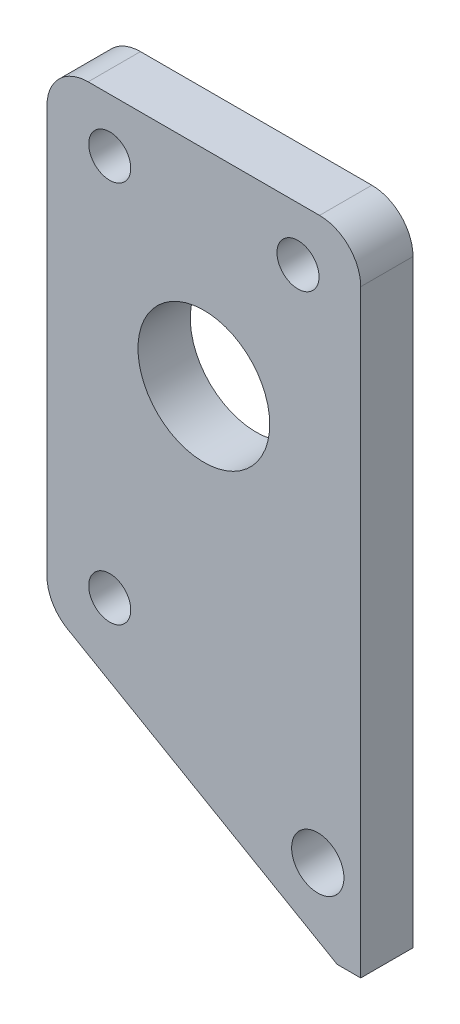
SolidWorks part; units mm, degrees
material "6061-T6 (SS)"
ref_plane "Front" through (0, 0, 0) normal (0, 0, 1) x (1, 0, 0)
ref_plane "Top" through (0, 0, 0) normal (0, 1, 0) x (1, 0, 0)
ref_plane "Right" through (0, 0, 0) normal (1, 0, 0) x (0, 0, -1)
ref_axis "side-side" through (80.9, 0, 0) along (-1, 0, 0)
ref_axis "up-down" through (0, 50, 0) along (0, -1, 0)
ref_axis "front-back" through (0, 0, -80.9) along (0, 0, 1)
sketch "Sketch4" plane through (0, 0, 0) normal (0, 0, 1) x (1, 0, 0)
  line L2 (23.3591, -238.4) -> (20.1841, -238.4)
  line L3 (20.1841, -238.4) -> (20.1841, -258.4435)
  line L5 (-176.6409, -178.2) -> (23.3591, -178.2)
  circle A2 centre (13.8341, -246.4) radius 3.175
  arc A3 (20.1841, -258.4435) -> (-67.8159, -304.4) centre (-11.8159, -304.4) ccw
sketch "Sketch1" plane through (0, 0, 0) normal (0, 0, 1) x (1, 0, 0)
  line L0 (16.1841, -255.9026) -> (-19.05, -235.5602)
  line L2 (-19.05, -178.2) -> (-19.05, -235.5602)
  line L3 (16.1841, -255.9026) -> (19.05, -255.9026)
  line L4 (19.05, -178.2) -> (19.05, -255.9026)
  line L5 (-176.6409, -178.2) -> (23.3591, -178.2) construction
  line L6 (-19.05, -178.2) -> (19.05, -178.2)
  circle A2 centre (13.8341, -246.4) radius 3.175
  circle A4 centre (-11.43, -231.16) radius 3.175 construction
  circle A6 centre (0, -203.2) radius 8
  circle A7 centre (-11.43, -184.7) radius 3.175 construction
  circle A8 centre (11.43, -184.7) radius 3.175 construction
  point P0 (0, 0)
  dimension "D7" = 18.5
  dimension "D8" = 16
  dimension "D11" = 52.7026
  dimension "D2" = 7.62
  dimension "D5" = 7.62
  dimension "D6" = 15.24
  dimension "D9" = 37.5497
  dimension "D10" = 60
extrude "Boss-Extrude1" add sketch "Sketch1" along normal blind 6.35
fillet "Fillet1" radius 5 3 edges at (-19.05, -235.5602, 3.175) (-19.05, -178.2, 3.175) (19.05, -178.2, 3.175)
hole_wizard "1/4-20 Tapped Hole1" positions "Sketch5" profile "Sketch6" tap size "1/4-20" standard "ANSI Inch"
sketch "Sketch5" plane through (0, 0, 6.35) normal (0, 0, 1) x (1, 0, 0)
  point P0 (-11.43, -184.7)
  point P2 (-11.43, -231.16)
  point P4 (11.43, -184.7)
sketch "Sketch6" plane through (-11.43, -184.7, 6.35) normal (1, 0, 0) x (0, -1, 0)
  line L0 (0, 0) -> (0, 20.5838)
  line L1 (0, 20.5838) -> (2.5527, 19.05)
  line L2 (2.5527, 19.05) -> (2.5527, 0)
  line L5 (2.5527, 0) -> (0, 0)
  line L10 (0, 20.5838) -> (-2.5527, 19.05) construction
  line L11 (0, -6.35) -> (0, 107.95) construction
  dimension "Tap Drill Dia." = 5.1054
  dimension "Tap Drill Depth" = 19.05
  dimension "Drill Angle" = 118
